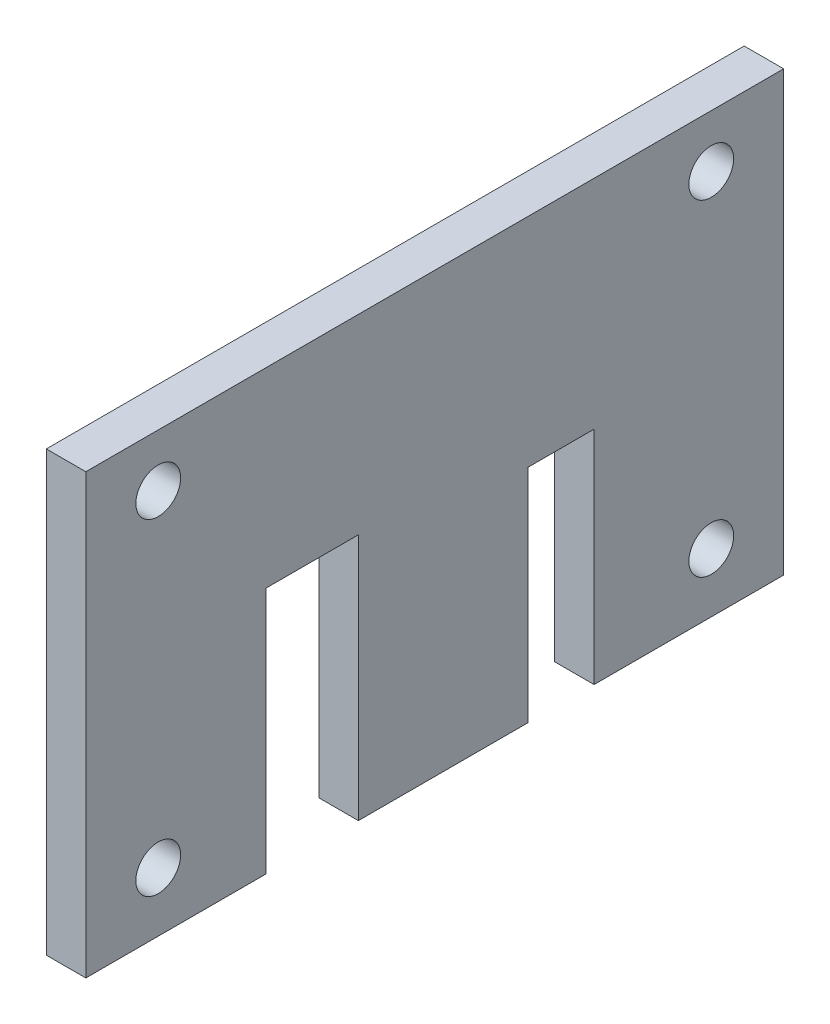
SolidWorks part; units mm, degrees
ref_plane "Front Plane" through (0, 0, 0) normal (0, 0, 1) x (1, 0, 0)
ref_plane "Top Plane" through (0, 0, 0) normal (0, 1, 0) x (1, 0, 0)
ref_plane "Right Plane" through (0, 0, 0) normal (1, 0, 0) x (0, 0, -1)
ref_plane "PX72_4" through (72.4, 0, 0) normal (1, 0, 0) x (0, 0, -1)
sketch "Sketch1" plane through (72.4, 0, 0) normal (1, 0, 0) x (0, 0, -1)
  line L0 (-99.5, -26.8) -> (-46.5, -26.8)
  line L1 (-46.5, -26.8) -> (-46.5, 6.5)
  line L2 (-46.5, 6.5) -> (-99.5, 6.5)
  line L3 (-99.5, 6.5) -> (-99.5, -26.8)
extrude "Cover Plate" add sketch "Sketch1" along normal blind 3
ref_plane "PX71_4" through (71.4, 0, 0) normal (1, 0, 0) x (0, 0, -1)
sketch "Sketch2" plane through (71.4, 0, 0) normal (1, 0, 0) x (0, 0, -1)
  line L0 (-85.8, -27.8) -> (-78.8, -27.8)
  line L1 (-78.8, -27.8) -> (-78.8, -8)
  line L2 (-78.8, -8) -> (-85.8, -8)
  line L3 (-85.8, -8) -> (-85.8, -27.8)
  line L4 (-65.9, -27.8) -> (-60.9, -27.8)
  line L5 (-60.9, -27.8) -> (-60.9, -10)
  line L6 (-60.9, -10) -> (-65.9, -10)
  line L7 (-65.9, -10) -> (-65.9, -27.8)
extrude "Cable Notches" cut sketch "Sketch2" along normal blind 5
sketch "Sketch3" plane through (71.4, 0, 0) normal (1, 0, 0) x (0, 0, -1)
  circle A0 centre (-94, -22.3) radius 1.7
  circle A1 centre (-94, 2.5) radius 1.7
  circle A2 centre (-52, -22.3) radius 1.7
  circle A3 centre (-52, 2.5) radius 1.7
extrude "Screw Holes" cut sketch "Sketch3" along normal blind 5
equation "\"BOARD_REAR\" = 86.0"
equation "\"BOARD_FRONT\" = 41.0"
equation "\"BOARD_END\" = 22.0"
equation "\"BOARD_ANGLED\" = 30.0"
equation "\"BOARD_DEPTH\" = 41.8431"
equation "\"PCB_T\" = 1.6"
equation "\"ABOVE_PCB\" = 14.0"
equation "\"BELOW_PCB\" = 6.0"
equation "\"MID_PARTS_H\" = 9.0"
equation "\"BOARD_HOLE_PILOT\" = 1.6"
equation "\"J2_X\" = 19.0"
equation "\"DUPONT_DROP\" = 14.0"
equation "\"BEND_R\" = 5.0"
equation "\"BOARD_GAP\" = 3.0"
equation "\"TOF_FOV\" = 25.0"
equation "\"TOF_MARGIN_DEG\" = 5.0"
equation "\"TOF_WIN_MARGIN\" = 1.0"
equation "\"TOF_Z\" = 9.0"
equation "\"TOF_SIDE_BEARING\" = 90.0"
equation "\"TOF_CONE_LEN\" = 70.0"
equation "\"CAM_W\" = 29.2"
equation "\"CAM_H\" = 28.2"
equation "\"CAM_D\" = 12.35"
equation "\"CAM_FRONT_Y\" = 43.0"
equation "\"CAM_BOTTOM_Z\" = 17.0"
equation "\"CAM_LENS_UP\" = 11.6"
equation "\"CAM_LENS_OPEN\" = 9.6"
equation "\"CAM_HFOV\" = 53.5"
equation "\"CAM_VFOV\" = 41.41"
equation "\"CAM_FOV_MARGIN\" = 3.0"
equation "\"CAM_FIT\" = 0.3"
equation "\"RIBBON_W\" = 16.0"
equation "\"RIBBON_T\" = 0.3"
equation "\"RIBBON_LEN\" = 150.0"
equation "\"RIBBON_EXIT_Y\" = 35.0"
equation "\"WALL\" = 2.4"
equation "\"HEAD_X\" = 48.4"
equation "\"HEAD_REAR_Y\" = -11.9"
equation "\"CAM_FOAM\" = 2.8"
equation "\"HEAD_FRONT_Y\" = 48.2"
equation "\"HEAD_TOP_Z\" = 50.6"
equation "\"HEAD_BOT_Z\" = -28.4"
equation "\"HEAD_SPLIT_Z\" = -4.0"
equation "\"SKIRT_T\" = 1.2"
equation "\"SKIRT_H\" = 3.0"
equation "\"SKIRT_FIT\" = 0.3"
equation "\"VISOR\" = 7.8"
equation "\"VISOR_Z\" = 40.0"
equation "\"ROOF_SLOPE_Y\" = 40.0"
equation "\"ROOF_CHAMFER\" = 10.0"
equation "\"REAR_CHAMFER\" = 10.0"
equation "\"CORNER_CHAMFER\" = 6.0"
equation "\"LOWER_SIDE_FACET\" = 6.0"
equation "\"LIGHTBAR_DEPTH\" = 1.0"
equation "\"HOOD_Z\" = 14.0"
equation "\"HOOD_L\" = 6.0"
equation "\"SIDE_HOOD_L\" = 4.0"
equation "\"INSERT_M3_D\" = 4.0"
equation "\"INSERT_M3_L\" = 6.0"
equation "\"M3_CLEAR\" = 3.4"
equation "\"M2_PILOT\" = 1.6"
equation "\"M25_PILOT\" = 2.2"
equation "\"BOX_X\" = 72.4"
equation "\"BOX_FRONT_Y\" = -11.9"
equation "\"BOX_REAR_Y\" = -124.4"
equation "\"BOX_BOT_Z\" = -28.4"
equation "\"BOX_TOP_Z\" = 28.0"
equation "\"LID_T\" = 2.4"
equation "\"LID_SKIRT\" = 1.6"
equation "\"LID_TONGUE_H\" = 3.0"
equation "\"LID_FIT\" = 0.3"
equation "\"PI_STANDOFF\" = 10.0"
equation "\"BOX_REAR_CHAMFER\" = 8.0"
equation "\"BOX_REAR_FACET\" = 4.0"
equation "\"VENT_UPSTAND\" = 3.0"
equation "\"TUBE_D\" = 22.2"
equation "\"TUBE_LINER\" = 1.0"
equation "\"MOUNT_Y\" = -70.0"
equation "\"RAIL_W\" = 30.0"
equation "\"RAIL_W2\" = 38.0"
equation "\"RAIL_H\" = 6.0"
equation "\"SLIDE\" = 0.3"
equation "\"STOP_T\" = 6.0"
equation "\"CLAMP_W\" = 40.0"
equation "\"CLAMP_HALF\" = 20.0"
equation "\"CLAMP_DROP\" = 12.0"
equation "\"CAP_T\" = 12.0"
equation "\"CLAMP_BOLT_OFF\" = 16.6"
equation "\"M5_INSERT_D\" = 6.4"
equation "\"M5_CLEAR\" = 5.5"
equation "\"LOCK_D\" = 3.3"
equation "\"POD_TILT_DEG\" = 0.0"
equation "\"PRINT_LIMIT\" = 180.0"
equation "\"PI5_L\" = 85.0"
equation "\"PI5_W\" = 56.0"
equation "\"PI5_T\" = 1.6"
equation "\"PI5_USBC_BX\" = 11.2"
equation "\"PI5_ETH_BY\" = 10.2"
equation "\"PI5_PORT_OVERHANG\" = 3.0"
equation "\"PI5_FPC_H\" = 5.0"
equation "\"PI5_FPC_USE\" = 0.0"
equation "\"PI5_PIN1_BX\" = 8.37"
equation "\"HEADER_BASE_H\" = 2.5"
equation "\"DUPONT_L\" = 14.0"
equation "\"PI5_UNDERSIDE\" = 1.5"
equation "\"COOLER_H\" = 15.0"
equation "\"HAT_W\" = 65.0"
equation "\"HAT_D\" = 56.5"
equation "\"HAT_T\" = 1.6"
equation "\"HAT_SPACER\" = 16.0"
equation "\"HAILO_H\" = 10.0"
equation "\"STACK_PINS_H\" = 6.0"
equation "\"DUPONT_SEAT\" = 0.5"
equation "\"PCIE_FFC_LOOP\" = 6.0"
equation "\"HAILO_AIR_GAP_MIN\" = 8.0"
equation "\"M25_CLEAR\" = 2.7"
equation "\"PI_X0\" = -55.0"
equation "\"PI_Y1\" = -36.5"
equation "\"PI_Y0\" = -92.5"
equation "\"BOX_LEN\" = 112.5"
equation "\"COVER_T\" = 3.0"
equation "\"COVER_TOP_Z\" = 6.5"
equation "\"SIDE_LEDGE_Z\" = -0.5"
equation "\"UPPER_LEDGE_Z\" = 17.0"
equation "\"REAR_LEDGE_Z\" = 8.0"
equation "\"LEDGE_L\" = 4.0"
equation "\"LEDGE_TIP\" = 1.5"
equation "\"RIBBON_W_PI\" = 11.5"
equation "\"RIBBON_RUN_Z\" = 12.0"
equation "\"RIBBON_SPEC_LEN\" = 200.0"
